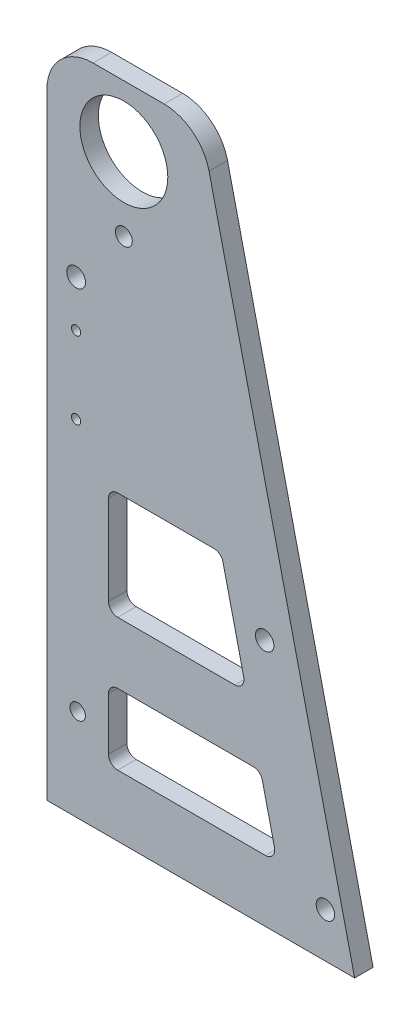
SolidWorks part; units mm, degrees
material "Policarbonato"
ref_plane "Plano frontal" through (0, 0, 0) normal (0, 0, 1) x (1, 0, 0)
ref_plane "Plano superior" through (0, 0, 0) normal (0, 1, 0) x (1, 0, 0)
ref_plane "Plano direito" through (0, 0, 0) normal (1, 0, 0) x (0, 0, -1)
sketch "Esboço1" plane through (0, 0, 0) normal (0, 0, 1) x (1, 0, 0)
  line L0 (0, 0) -> (0, 215)
  line L2 (100, 0) -> (0, 0)
  line L3 (0, 215) -> (50, 215)
  line L4 (50, 215) -> (100, 0)
  line L5 (10, 103) -> (10, 15) construction
  line L6 (25, 215) -> (25, 175) construction
  line L7 (10, 15) -> (75.7552, 15) construction
  line L8 (75.7552, 15) -> (55.2901, 103) construction
  line L9 (55.2901, 103) -> (10, 103) construction
  line L10 (20, 95) -> (20, 66)
  line L11 (23, 63) -> (61.0374, 63)
  line L12 (63.9594, 66.6795) -> (57.2152, 95.6795)
  line L13 (54.2932, 98) -> (23, 98)
  line L14 (20, 40) -> (20, 23)
  line L15 (23, 20) -> (71.0374, 20)
  line L16 (73.9594, 23.6795) -> (70.0059, 40.6795)
  line L17 (23, 43) -> (67.0839, 43)
  line L18 (0, 195) -> (50, 195) construction
  line L23 (17, 205) -> (33, 185) construction
  line L24 (17, 185) -> (33, 205) construction
  arc A8 (70.0059, 40.6795) -> (67.0839, 43) centre (67.0839, 40) ccw
  arc A9 (71.0374, 20) -> (73.9594, 23.6795) centre (71.0374, 23) ccw
  arc A10 (20, 23) -> (23, 20) centre (23, 23) ccw
  arc A11 (20, 40) -> (23, 43) centre (23, 40) cw
  arc A12 (57.2152, 95.6795) -> (54.2932, 98) centre (54.2932, 95) ccw
  arc A13 (61.0374, 63) -> (63.9594, 66.6795) centre (61.0374, 66) ccw
  arc A14 (20, 66) -> (23, 63) centre (23, 66) ccw
  arc A15 (20, 95) -> (23, 98) centre (23, 95) cw
  circle A20 centre (25, 195) radius 14.2875
  circle A21 centre (10, 30) radius 2.5
  point P8 (25, 195)
  point P49 (20, 63)
  dimension "D3" = 20
  dimension "D4" = 16
  dimension "D7" = 28.575
  dimension "D21" = 3
  dimension "D20" = 10
  dimension "D22" = 5
  dimension "D1" = 215
  dimension "D2" = 100
  dimension "D5" = 50
  dimension "D9" = 20
  dimension "D10" = 20
  dimension "D11" = 10
  dimension "D12" = 20
  dimension "D13" = 15
  dimension "D14" = 20
  dimension "D15" = 10
  dimension "D16" = 29
  dimension "D17" = 17
  dimension "D18" = 10
  dimension "D19" = 30
  dimension "D8" = 20
extrude "Ressalto-extrusão2" add sketch "Esboço1" along normal blind 6
fillet "Filete1" radius 15 2 edges at (0, 215, 3) (50, 215, 3)
sketch "Esboço3" plane through (0, 0, 0) normal (0, 0, -1) x (-1, 0, 0)
  line L1 (0, 0) -> (-100, 0) construction
  line L2 (0, 200) -> (0, 0) construction
  circle A0 centre (-9.5, 112) radius 1.5
  circle A1 centre (-90.5, 14.5) radius 3
  circle A2 centre (-9.5, 137) radius 1.5
  circle A3 centre (-9.5, 152) radius 3.05
  point P6 (-9.5, 112)
  point P9 (-9.5, 137)
  dimension "D5" = 6
  dimension "D1" = 25
  dimension "D6" = 3
  dimension "D7" = 112
  dimension "D8" = 15
  dimension "D9" = 6.1
  dimension "D2" = 9.5
  dimension "D3" = 14.5
  dimension "D4" = 9.5
extrude "Corte-extrusão1" cut sketch "Esboço3" against normal through all
sketch "Esboço5" plane through (0, 0, 0) normal (0, 0, -1) x (-1, 0, 0)
  circle A0 centre (-25, 171.1875) radius 2.75
  circle A1 centre (-70.7598, 80.3986) radius 3
  circle A2 centre (-25, 195) radius 14.2875 construction
  point P6 (-25, 195)
  point P7 (0, 0)
  dimension "D1" = 23.8125
  dimension "D2" = 5.5
extrude "Corte-extrusão2" cut sketch "Esboço5" against normal through all
